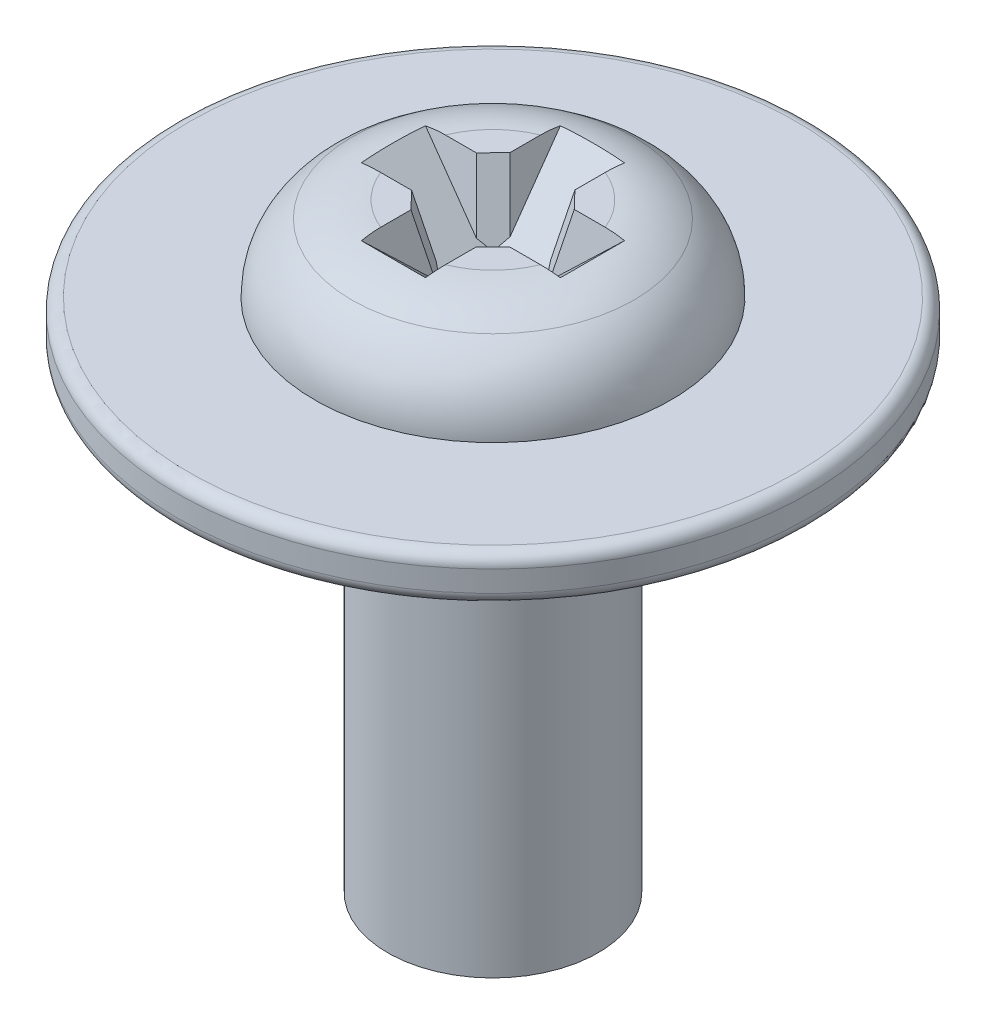
SolidWorks part; units mm, degrees
material "Plain Carbon Steel"
ref_plane "Front Plane" through (0, 0, 0) normal (0, 0, 1) x (1, 0, 0)
ref_plane "Top Plane" through (0, 0, 0) normal (0, 1, 0) x (1, 0, 0)
ref_plane "Right Plane" through (0, 0, 0) normal (1, 0, 0) x (0, 0, -1)
sketch "Sketch1" plane through (0, 0, 0) normal (0, 0, 1) x (1, 0, 0)
  line L0 (0, 7.4) -> (0, 0)
  line L1 (-1.3, 5.8) -> (-3.9, 5.8)
  line L2 (-3.9, 5.8) -> (-3.9, 6.36)
  line L3 (-3.9, 6.36) -> (-2.2, 6.36)
  line L4 (-1.3, 5.8) -> (-1.3, 0)
  line L5 (-1.3, 0) -> (0, 0)
  line L6 (0, 7.4) -> (-1.0644, 7.4)
  arc A1 (-2.2, 6.36) -> (-1.7426, 7.2) centre (-1.2, 6.36) cw
  arc A2 (-1.7426, 7.2) -> (-1.0644, 7.4) centre (-1.0644, 6.15) cw
  dimension "D1" = 2.6
  dimension "D8" = 2
  dimension "D9" = 2.5
  dimension "D2" = 0.56
  dimension "D3" = 4.4
  dimension "D4" = 5.8
  dimension "D5" = 7.8
  dimension "D6" = 7.4
revolve "Revolve1" add sketch "Sketch1" angle 360 about L0
fillet "Fillet1" radius 0.15 2 edges at (-3.9, 5.8, 0) (-3.9, 6.36, 0)
sketch "Sketch2" plane through (0, 7.4, 0) normal (0, 1, 0) x (1, 0, 0)
  line L1 (-0.4, -1.25) -> (0.4, -1.25)
  line L2 (-0.4, -1.25) -> (-0.4, 1.25)
  line L3 (-0.4, 1.25) -> (0.4, 1.25)
  line L4 (0.4, -1.25) -> (0.4, 1.25)
  line L5 (-0.4, -1.25) -> (0.4, 1.25) construction
  line L6 (-0.4, 1.25) -> (0.4, -1.25) construction
  point P0 (0, 0)
  dimension "D1" = 2.5
  dimension "D2" = 0.8
ref_plane "Plane1" through (0, 6.4, 0) normal (0, 1, 0) x (1, 0, 0)
sketch "Sketch3" plane through (0, 6.4, 0) normal (0, 1, 0) x (1, 0, 0)
  line L1 (0.2, 0.2) -> (-0.2, 0.2)
  line L2 (0.2, 0.2) -> (0.2, -0.2)
  line L3 (0.2, -0.2) -> (-0.2, -0.2)
  line L4 (-0.2, 0.2) -> (-0.2, -0.2)
  line L5 (0.2, 0.2) -> (-0.2, -0.2) construction
  line L6 (0.2, -0.2) -> (-0.2, 0.2) construction
  point P0 (0, 0)
  dimension "D1" = 0.4
loft "Cut-Loft1" cut profiles "Sketch2", "Sketch3"
pattern_circular "CirPattern1" count 2 over 90 about axis through (0, 0, 0) along (0, 1, 0) of "Cut-Loft1"
chamfer "Chamfer1" distance 0.2 angle 45 4 edges
